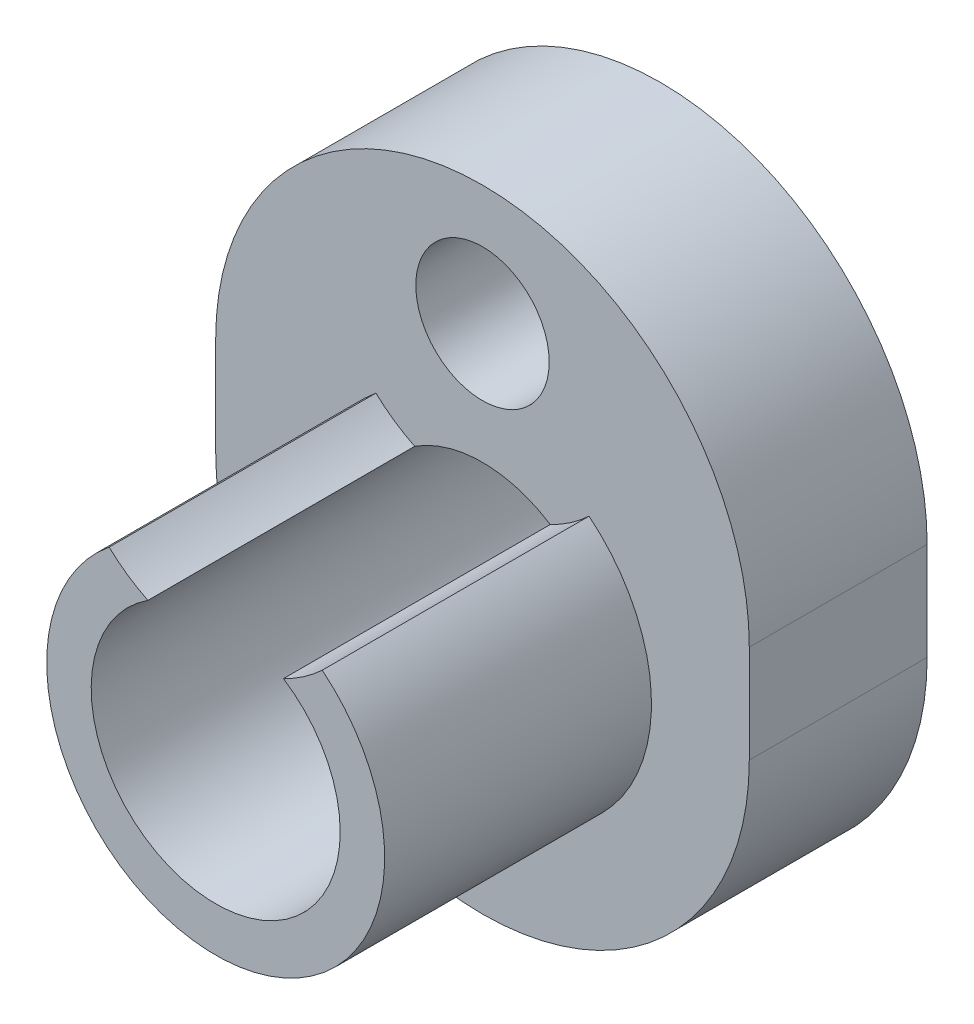
SolidWorks part; units mm, degrees
ref_plane "Płaszczyzna przednia" through (0, 0, 0) normal (0, 0, 1) x (1, 0, 0)
ref_plane "Płaszczyzna górna" through (0, 0, 0) normal (0, 1, 0) x (1, 0, 0)
ref_plane "Płaszczyzna prawa" through (0, 0, 0) normal (1, 0, 0) x (0, 0, -1)
sketch "Sketch1" plane through (0, 0, 0) normal (0, 0, 1) x (1, 0, 0)
  line L0 (0.022, -3.2427) -> (0.022, 34.4365) construction
  line L2 (-5.978, 22.118) -> (-5.978, 19.918)
  line L3 (6.022, 22.118) -> (6.022, 19.918)
  circle A0 centre (0.022, 19.918) radius 2.8
  circle A1 centre (0.022, 19.918) radius 6
  circle A2 centre (0.022, 25.418) radius 1.5
  circle A3 centre (0.022, 22.118) radius 6
  circle A4 centre (0.022, 19.918) radius 3.8
  circle A6 centre (0.022, 25.418) radius 3.5
  dimension "D1" = 5.6
  dimension "D3" = 3
  dimension "D4" = 12
  dimension "D5" = 1
  dimension "D2" = 12
  dimension "D7" = 2
  dimension "D6" = 5.5
extrude "Boss-Extrude3" add sketch "Sketch1" along normal blind 4 contours A2 L0 A1 | L0 A2 A1 | A1 A3 | A3 A1 | A4 A3 A1 | L0 A4 A1 A2 | L0 A4 | A4 L0 A2 A1 | L0 A4 | A4 L0 A0 | A1 A3 A4 | L0 A4 A0 | L0 A1 A3 | A1 L0 A3 | A3 L2 A1 | A3 A1 L3 region at (-2.9612, 16.2789, 0) region at (3.0052, 16.2789, 0) region at (-3.486, 18.6724, 0) region at (4.214, 21.0057, 0) region at (-4.17, 21.0057, 0) region at (0.0995, 16.618, 0) region at (-5.9475, 21.018, 0) region at (5.9915, 21.018, 0) region at (-4.644, 24.5848, 0) region at (4.688, 24.5848, 0) region at (-2.0382, 24.2742, 0) region at (-1.0248, 23.0259, 0) region at (-1.8612, 26.7209, 0) region at (2.0822, 24.2742, 0) region at (1.9052, 26.7209, 0) region at (1.0688, 23.0259, 0)
extrude "Boss-Extrude5" add sketch "Sketch1<8>" along normal blind 10 contours A4 L0 A0 A6 | L0 A4 A6 A0 region at (-3.486, 18.6724, 0) region at (0.0995, 16.618, 0)
sketch "Sketch1<8>" plane through (0, 0, 0) normal (0, 0, 1) x (1, 0, 0) same geometry as "Sketch1"
